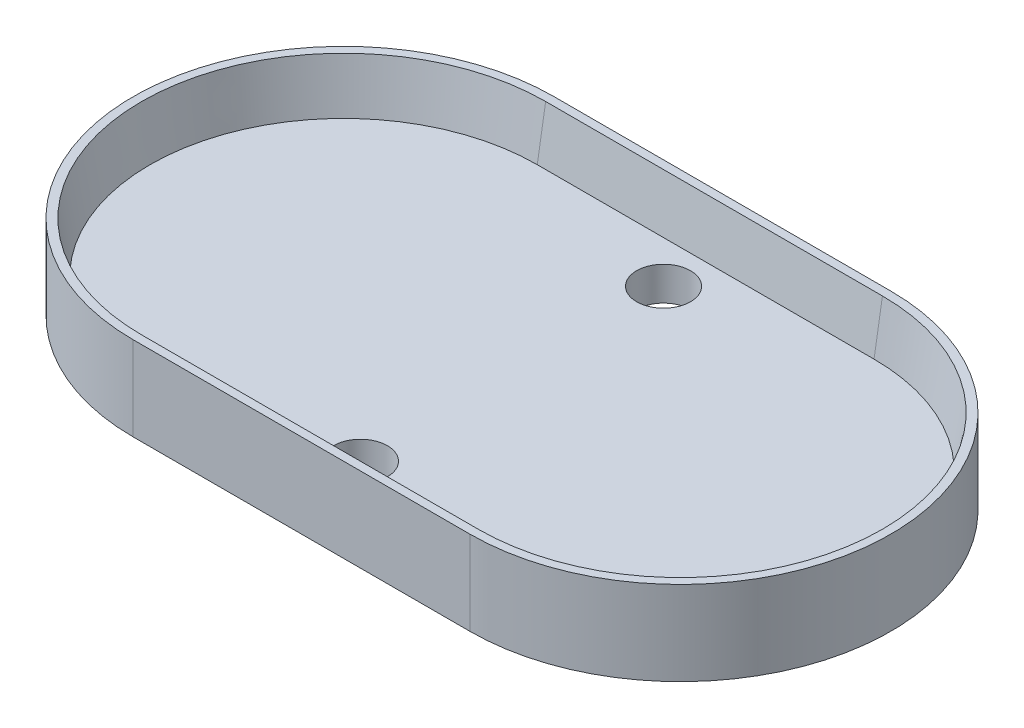
SolidWorks part; units mm, degrees
ref_plane "Front Plane" through (0, 0, 0) normal (0, 0, 1) x (1, 0, 0)
ref_plane "Top Plane" through (0, 0, 0) normal (0, 1, 0) x (1, 0, 0)
ref_plane "Right Plane" through (0, 0, 0) normal (1, 0, 0) x (0, 0, -1)
sketch "Sketch1" plane through (0, 0, 0) normal (0, 1, 0) x (1, 0, 0)
  line L0 (-10, 0) -> (10, 0)
  line L1 (10, 0) -> (21, 0)
  line L2 (0, -12.5) -> (0, 12.5)
  line L3 (-10, 12.5) -> (10, 12.5)
  line L4 (0, 16.9432) -> (0, -18.2998) construction
  line L5 (25.2799, 0) -> (-28.0829, 0) construction
  line L7 (-10, -12.5) -> (10, -12.5)
  arc A0 (10, -12.5) -> (10, 12.5) centre (10, 0) ccw
  arc A1 (-10, -12.5) -> (-10, 12.5) centre (-10, 0) cw
  point P16 (0, 0)
  dimension "D2" = 12.5
  dimension "D1" = 10
  dimension "D3" = 10
extrude "Boss-Extrude1" add sketch "Sketch1" along normal blind 2 contours A1 L0 L2 L3 | A1 L7 L2 L0 | L1 A0 L3 L2 L0 | L7 A0 L1 L0 L2 region at (-10.1051, 0, 0) region at (0.3363, 0, 6.25)
sketch "Sketch2" plane through (0, 2, 0) normal (0, 1, 0) x (1, 0, 0)
  line L4 (-10, -11.5) -> (10, -11.5)
  line L5 (10, 11.5) -> (-10, 11.5)
  line L6 (-10, -11.5) -> (10, -11.5)
  line L7 (10, 11.5) -> (-10, 11.5)
  line L10 (10, 12.5) -> (-10, 12.5)
  line L11 (-10, -12.5) -> (10, -12.5)
  line L12 (10, 12.5) -> (-10, 12.5)
  line L13 (-10, -12.5) -> (10, -12.5)
  arc A4 (10, -11.5) -> (10, 11.5) centre (10, 0) ccw
  arc A5 (-10, 11.5) -> (-10, -11.5) centre (-10, 0) ccw
  arc A6 (10, -11.5) -> (10, 11.5) centre (10, 0) ccw
  arc A7 (-10, 11.5) -> (-10, -11.5) centre (-10, 0) ccw
  arc A10 (-10, 12.5) -> (-10, -12.5) centre (-10, 0) ccw
  arc A11 (10, -12.5) -> (10, 12.5) centre (10, 0) ccw
  arc A12 (-10, 12.5) -> (-10, -12.5) centre (-10, 0) ccw
  arc A13 (10, -12.5) -> (10, 12.5) centre (10, 0) ccw
  dimension "D1" = 1
  dimension "D2" = 0
extrude "Boss-Extrude2" add sketch "Sketch2" along normal blind 3
chamfer "Chamfer1" distance 0.5 distance2 3 4 edges at (0, 5, 11.5) (21.5, 5, 0) (0, 5, -11.5) (-21.5, 5, 0) first distance on face at (0, 5, 0)
sketch "Sketch3" plane through (0, 0, 0) normal (0, -1, 0) x (1, 0, 0)
  line L0 (-10, 12.5) -> (10, 12.5) construction
  line L1 (-10, -12.5) -> (10, -12.5) construction
  circle A0 centre (0, -9) radius 1.6
  circle A1 centre (0, 9) radius 1.6
  dimension "D1" = 3.2
  dimension "D2" = 3.2
  dimension "D3" = 3.5
  dimension "D4" = 3.5
extrude "Cut-Extrude1" cut sketch "Sketch3" against normal through all
